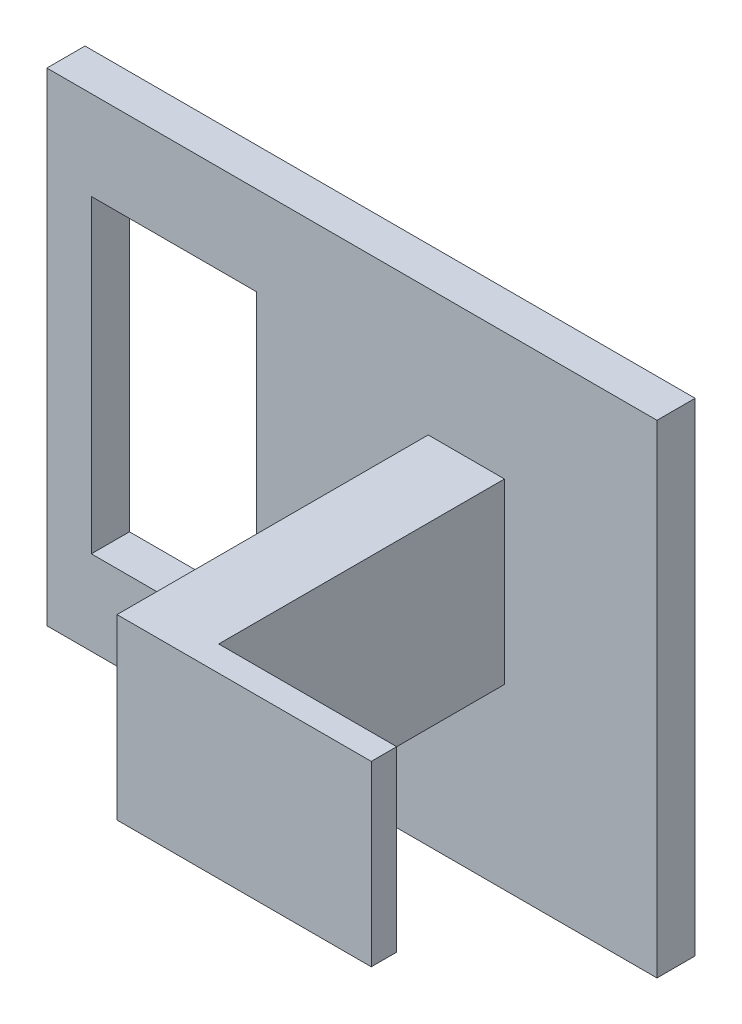
SolidWorks part; units mm, degrees
ref_plane "Front Plane" through (0, 0, 0) normal (0, 0, 1) x (1, 0, 0)
ref_plane "Top Plane" through (0, 0, 0) normal (0, 1, 0) x (1, 0, 0)
ref_plane "Right Plane" through (0, 0, 0) normal (1, 0, 0) x (0, 0, -1)
sketch "Sketch1" plane through (0, 0, 0) normal (0, 0, 1) x (1, 0, 0)
  line L1 (-70, 0) -> (-22, 0)
  line L2 (-70, 0) -> (-70, 38)
  line L3 (-70, 38) -> (-22, 38)
  line L4 (-22, 0) -> (-22, 38)
  line L6 (-66.5, 6.65) -> (-53.5, 6.65)
  line L7 (-66.5, 6.65) -> (-66.5, 31)
  line L8 (-66.5, 31) -> (-53.5, 31)
  line L9 (-53.5, 6.65) -> (-53.5, 31)
extrude "Servo_Shelf" add sketch "Sketch1" along normal blind 3 from offset 27.48 offset against normal yes
sketch "Sketch2" plane through (0, 0, 0) normal (0, 0, 1) x (1, 0, 0)
  line L1 (-40, 14) -> (-34, 14)
  line L2 (-40, 14) -> (-40, 28)
  line L3 (-40, 28) -> (-34, 28)
  line L4 (-34, 14) -> (-34, 28)
extrude "Outboard_Riser" add sketch "Sketch2" along normal blind 24.48 from offset 25.48 offset against normal yes
sketch "Sketch3" plane through (0, 0, 0) normal (0, 0, 1) x (1, 0, 0)
  line L1 (-40, 14) -> (-20, 14)
  line L2 (-40, 14) -> (-40, 28)
  line L3 (-40, 28) -> (-20, 28)
  line L4 (-20, 14) -> (-20, 28)
extrude "Plate_Attachment_Foot" add sketch "Sketch3" along normal blind 2 from offset 2 offset against normal yes
